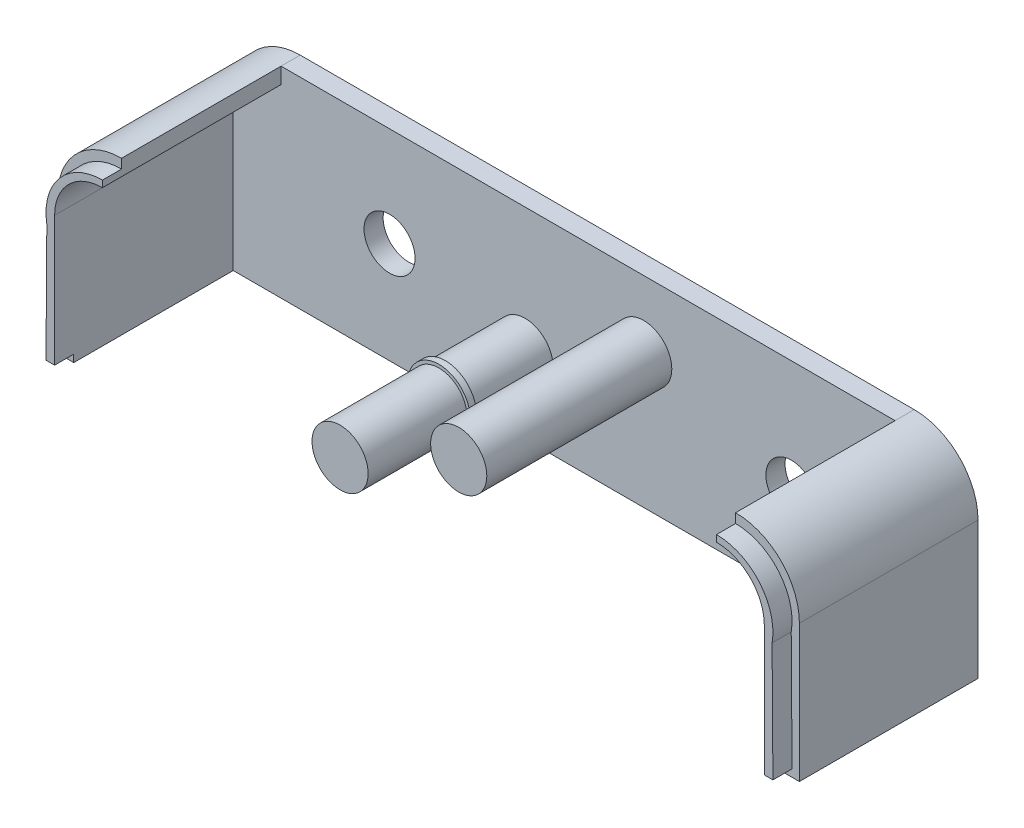
SolidWorks part; units mm, degrees
ref_plane "Front Plane" through (0, 0, 0) normal (0, 0, 1) x (1, 0, 0)
ref_plane "Top Plane" through (0, 0, 0) normal (0, 1, 0) x (1, 0, 0)
ref_plane "Right Plane" through (0, 0, 0) normal (1, 0, 0) x (0, 0, -1)
sketch "Sketch1" plane through (0, 0, 0) normal (0, 0, 1) x (1, 0, 0)
  line L0 (58.125, -1.75) -> (-58.125, -1.75) construction
  line L1 (-48.125, 15.75) -> (48.125, 15.75)
  line L2 (-58.125, 5.75) -> (-58.125, -15.75)
  line L3 (-58.125, -15.75) -> (58.125, -15.75)
  line L4 (58.125, 5.75) -> (58.125, -15.75)
  line L5 (-58.125, 15.75) -> (58.125, -15.75) construction
  line L6 (-58.125, -15.75) -> (58.125, 15.75) construction
  line L7 (31.875, 15.75) -> (31.875, -15.75) construction
  line L8 (-31.125, -15.75) -> (-31.125, 15.75) construction
  line L9 (-58.125, 0.15) -> (58.125, 0.15) construction
  arc A0 (48.125, 15.75) -> (58.125, 5.75) centre (48.125, 5.75) cw
  arc A1 (-48.125, 15.75) -> (-58.125, 5.75) centre (-48.125, 5.75) ccw
  circle A2 centre (31.875, -1.75) radius 4
  circle A3 centre (-31.125, 0.15) radius 4
  point P0 (0, 0)
  dimension "D3" = 10
  dimension "D6" = 8
  dimension "D8" = 8
  dimension "D1" = 116.25
  dimension "D2" = 31.5
  dimension "D4" = 14
  dimension "D5" = 26.25
  dimension "D7" = 15.9
  dimension "D9" = 27
extrude "Boss-Extrude2" add sketch "Sketch1" along normal blind 3
sketch "Sketch2" plane through (0, 0, 3) normal (0, 0, 1) x (1, 0, 0)
  line L0 (-17.875, 15.75) -> (-17.875, -15.75) construction
  line L1 (48.125, 15.75) -> (-48.125, 15.75) construction
  line L2 (-58.125, -15.75) -> (58.125, -15.75) construction
  line L3 (21.625, 15.75) -> (21.625, -15.75) construction
  line L4 (-58.125, 5.25) -> (58.125, 5.25) construction
  line L5 (-58.125, 5.75) -> (-58.125, -15.75) construction
  line L6 (58.125, -15.75) -> (58.125, 5.75) construction
  line L7 (8.725, 15.75) -> (8.725, -15.75) construction
  line L8 (-9.875, 15.75) -> (-9.875, -15.75) construction
  line L9 (-58.125, -3.75) -> (58.125, -3.75) construction
  line L10 (0.575, 5.25) -> (0.575, -15.75) construction
  line L11 (-18.025, -3.75) -> (-18.025, -15.75) construction
  line L26 (55.625, -15.75) -> (55.625, 5.75)
  line L27 (55.625, -15.75) -> (55.625, 5.75)
  line L28 (-55.625, -15.75) -> (-58.125, -15.75)
  line L29 (-55.625, 5.75) -> (-55.625, -15.75)
  line L30 (-55.625, 5.75) -> (-55.625, -15.75)
  line L31 (-58.125, -15.75) -> (-58.125, 5.25)
  line L32 (-48.125, 13.25) -> (-48.125, 15.75)
  line L33 (55.625, -15.75) -> (58.125, -15.75)
  line L34 (58.125, -15.75) -> (58.125, 5.25)
  line L35 (48.125, 13.25) -> (48.125, 15.75)
  circle A0 centre (-31.125, 0.15) radius 13.25 construction
  circle A1 centre (31.875, -1.75) radius 10.25 construction
  circle A2 centre (8.725, 5.25) radius 18 construction
  circle A3 centre (8.725, 5.25) radius 4.4
  circle A4 centre (8.725, 5.25) radius 8.15 construction
  circle A5 centre (-9.875, -3.75) radius 8.15 construction
  circle A6 centre (-9.875, -3.75) radius 4.4
  arc A10 (58.125, 5.75) -> (48.125, 15.75) centre (48.125, 5.75) ccw
  arc A11 (58.125, 5.75) -> (48.125, 15.75) centre (48.125, 5.75) ccw
  arc A13 (-48.125, 15.75) -> (-58.125, 5.75) centre (-48.125, 5.75) ccw
  arc A14 (-48.125, 15.75) -> (-58.125, 5.75) centre (-48.125, 5.75) ccw
  arc A28 (55.625, 5.75) -> (48.125, 13.25) centre (48.125, 5.75) ccw
  arc A29 (55.625, 5.75) -> (48.125, 13.25) centre (48.125, 5.75) ccw
  arc A32 (-48.125, 13.25) -> (-55.625, 5.75) centre (-48.125, 5.75) ccw
  arc A33 (-48.125, 13.25) -> (-55.625, 5.75) centre (-48.125, 5.75) ccw
  line M2 (58.125, -15.75) -> (58.125, 5.75)
  arc M3 (58.125, 5.75) -> (48.125, 15.75) centre (48.125, 5.75) ccw
  arc M5 (-48.125, 15.75) -> (-58.125, 5.75) centre (-48.125, 5.75) ccw
  line M6 (-58.125, 5.75) -> (-58.125, -15.75)
  line M7 (-58.125, -15.75) -> (58.125, -15.75)
  dimension "D1" = 26.5
  dimension "D2" = 20.5
  dimension "D6" = 8.8
  dimension "D8" = 10.45
  dimension "D9" = 8.8
  dimension "D10" = 18.45
  dimension "D7" = 31.5
  dimension "D11" = 12
  dimension "16" = 16.3
  dimension "D12" = 16.3
  dimension "D13" = 36
  dimension "D14" = 8
  dimension "D16" = 2.5
  dimension "D3" = 39.5
  dimension "D4" = 12.9
  dimension "D15" = 0.15
  dimension "D20" = 21
  dimension "D17" = 2.5
  dimension "D18" = 0
  dimension "D19" = 0
other "AlignGroup1"
other "AlignGroup2"
other "AlignGroup3"
other "AlignGroup4"
other "AlignGroup5"
extrude "Boss-Extrude3" add sketch "Sketch2" along normal blind 25 contours A3 | A6 | A29 L27 L35 M7 M2 M3 | A33 L32 L30 M5 M6 M7 region at (55.6498, 1.3793, 3) region at (-55.6498, 1.3793, 3) region at (8.725, 5.25, 3) region at (-9.875, -3.75, 3)
sketch "Sketch5" plane through (0, 0, 28) normal (0, 0, 1) x (1, 0, 0)
  line L4 (-56.8469, 3.9347) -> (-56.975, -14.6)
  line L5 (0, 15.75) -> (0, -15.75) construction
  line L6 (48.125, 15.75) -> (-48.125, 15.75) construction
  line L7 (-55.625, -15.75) -> (55.625, -15.75) construction
  line L8 (-55.625, -14.6) -> (-56.975, -14.6)
  line L9 (-58.125, -15.75) -> (-55.625, -15.75) construction
  line L16 (55.625, -14.6) -> (55.625, 5.75)
  line L17 (48.125, 13.25) -> (48.125, 14.2852)
  line L18 (55.625, -14.6) -> (56.975, -14.6)
  line L19 (56.8469, 3.9347) -> (56.975, -14.6)
  line L28 (-48.125, 13.25) -> (-48.125, 15.75)
  line L29 (-58.125, 5.75) -> (-58.125, -15.75)
  line L30 (-58.125, -15.75) -> (-55.625, -15.75)
  line L31 (-55.625, -15.75) -> (-55.625, 5.75)
  line L32 (-48.125, 13.25) -> (-48.125, 14.2852)
  line L35 (-55.625, -14.6) -> (-55.625, 5.75)
  arc A2 (-48.125, 14.2852) -> (-56.8469, 3.9347) centre (-48.125, 5.4352) ccw
  arc A3 (48.125, 13.25) -> (55.625, 5.75) centre (48.125, 5.75) cw
  arc A4 (48.125, 14.2852) -> (56.8469, 3.9347) centre (48.125, 5.4352) cw
  arc A14 (-48.125, 13.25) -> (-55.625, 5.75) centre (-48.125, 5.75) ccw
  arc A15 (-48.125, 15.75) -> (-58.125, 5.75) centre (-48.125, 5.75) ccw
  arc A16 (-48.125, 13.25) -> (-55.625, 5.75) centre (-48.125, 5.75) ccw
  dimension "D1" = 1.35
  dimension "D3" = 0.3148
  dimension "D4" = 8.85
  dimension "D2" = 1.15
  dimension "D6" = 18.5352
  dimension "D5" = 0
sketch "Sketch10" plane through (0, 0, 28) normal (0, 0, 1) x (1, 0, 0)
  circle A1 centre (8.725, 5.25) radius 4.4
  circle A2 centre (8.725, 5.25) radius 4.4
  circle A3 centre (-9.875, -3.75) radius 4.4
  circle A4 centre (-9.875, -3.75) radius 4.4
  dimension "D1" = 0
  dimension "D2" = 0
extrude "Cut-Extrude3" cut sketch "Sketch10" against normal blind 1
extrude "Boss-Extrude5" add sketch "Sketch5" along normal blind 3
sketch "Sketch12" plane through (0, 0, 27) normal (0, 0, 1) x (1, 0, 0)
  circle A0 centre (-9.875, -3.75) radius 4.4 construction
  circle A1 centre (8.725, 5.25) radius 4.4 construction
  circle A2 centre (-9.875, -3.75) radius 4.4
  circle A3 centre (8.725, 5.25) radius 4.4
extrude "Boss-Extrude6" add sketch "Sketch12" along normal blind 5
ref_plane "Plane2" through (0, 0, 15.5) normal (0, 0, 1) x (1, 0, 0)
sketch "Sketch14" plane through (0, 0, 15.5) normal (0, 0, 1) x (1, 0, 0)
  circle A2 centre (-9.875, -3.75) radius 4.9
  circle A3 centre (-9.875, -3.75) radius 4.9
  dimension "D1" = 0.5
extrude "Boss-Extrude7" add sketch "Sketch14" along normal blind 1
